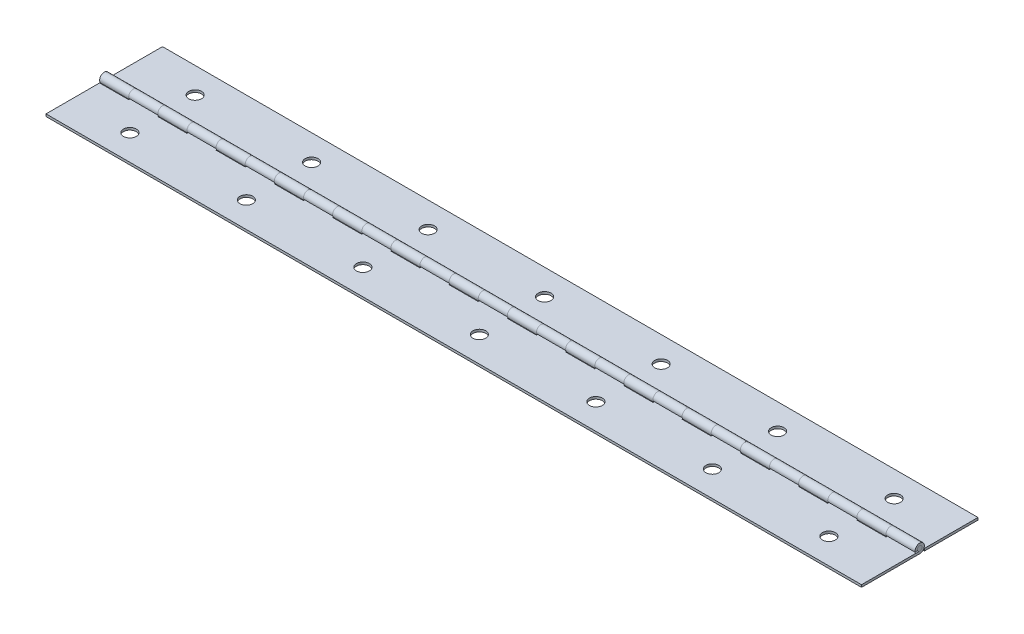
SolidWorks part; units mm, degrees
material "Plain Carbon Steel"
ref_plane "Front Plane" through (0, 0, 0) normal (0, 0, 1) x (1, 0, 0)
ref_plane "Top Plane" through (0, 0, 0) normal (0, 1, 0) x (1, 0, 0)
ref_plane "Right Plane" through (0, 0, 0) normal (1, 0, 0) x (0, 0, -1)
sketch "Sketch1" plane through (0, 0, 0) normal (1, 0, 0) x (0, 0, -1)
  line L0 (25.4, 1.016) -> (0, 1.016)
  line L1 (25.4, 0) -> (0, 0)
  line L2 (1.9675, 1.524) -> (0.9837, 1.778)
  line L3 (25.4, 1.016) -> (25.4, 0)
  circle A0 centre (0, 2.032) radius 1.016 construction
  arc A1 (0, 1.016) -> (0.9837, 1.778) centre (0, 2.032) cw
  arc A2 (0, 0) -> (1.9675, 1.524) centre (0, 2.032) cw
  arc A3 (0, 0) -> (1.9675, 1.524) centre (0, 2.032) cw construction
  dimension "D1" = 2.032
  dimension "D2" = 1.016
  dimension "D3" = 25.4
  dimension "D5" = 0.508
  dimension "D4" = 1.016
extrude "Boss-Extrude1" add sketch "Sketch1" along normal blind 1828.8
sketch "Sketch2" plane through (0, 1.016, 0) normal (0, 1, 0) x (1, 0, 0)
  line L0 (1828.8, 2.032) -> (0, 2.032) construction
  line L1 (12.7, 2.032) -> (25.4, 2.032)
  line L2 (12.7, 2.032) -> (12.7, -2.032)
  line L3 (12.7, -2.032) -> (25.4, -2.032)
  line L4 (25.4, 2.032) -> (25.4, -2.032)
  line L5 (0, -2.032) -> (1828.8, -2.032) construction
  dimension "D1" = 12.7
  dimension "D2" = 12.7
extrude "Cut-Extrude1" cut sketch "Sketch2" against normal through all both and the other way through all
pattern_linear "LPattern1" count 72 spacing 25.4 along (1, 0, 0) of "Cut-Extrude1"
sketch "Sketch3" plane through (0, 0, 0) normal (-1, 0, 0) x (0, 0, 1)
  line L1 (0, 0) -> (-25.4, 0) construction
  line L8 (25.4, 0) -> (0, 0)
  line L9 (25.4, 0) -> (25.4, 1.016)
  line L10 (25.4, 1.016) -> (0, 1.016)
  line L11 (-25.4, 1.016) -> (0, 1.016) construction
  line L12 (0.9837, 1.778) -> (1.9675, 1.524)
  arc A4 (0, 1.016) -> (0.9837, 1.778) centre (0, 2.032) cw
  arc A5 (0, 0) -> (1.9675, 1.524) centre (0, 2.032) cw
extrude "Boss-Extrude2" add sketch "Sketch3" against normal up to surface (1828.8 mm away) separate body up to face at (1828.8, 0.508, -13.716)
sketch "Sketch4" plane through (0, 1.016, 0) normal (0, 1, 0) x (1, 0, 0)
  line L1 (0, -2.032) -> (12.7, -2.032)
  line L2 (0, -2.032) -> (0, 2.032)
  line L3 (0, 2.032) -> (12.7, 2.032)
  line L4 (12.7, -2.032) -> (12.7, 2.032)
extrude "Cut-Extrude2" cut sketch "Sketch4" against normal through all both and the other way through all
pattern_linear "LPattern3" count 72 spacing 25.4 along (1, 0, 0) of "Cut-Extrude2"
sketch "Sketch5" plane through (0, 0, 0) normal (-1, 0, 0) x (0, 0, 1)
  circle A0 centre (0, 2.032) radius 1.016
  arc A1 (0, 1.016) -> (-0.9837, 1.778) centre (0, 2.032) ccw construction
extrude "Boss-Extrude4" add sketch "Sketch5" against normal up to surface (1828.8 mm away) separate body up to face at (1828.8, 1.6081, 8.4015)
hole_wizard "#2 (0.221) Diameter Hole1" positions "Sketch6" profile "Sketch7" hole size "#2" standard "ANSI Inch" end condition through all
sketch "Sketch6" plane through (0, 1.016, 0) normal (0, 1, 0) x (1, 0, 0)
  line L0 (1828.8, -25.4) -> (0, -25.4) construction
  line L1 (0, -25.4) -> (0, -2.032) construction
  point P0 (25.4, -14.224)
  point P12 (76.2, -14.224)
  point P13 (127, -14.224)
  point P14 (177.8, -14.224)
  point P15 (228.6, -14.224)
  point P16 (279.4, -14.224)
  point P17 (330.2, -14.224)
  point P18 (381, -14.224)
  point P19 (431.8, -14.224)
  point P20 (482.6, -14.224)
  point P21 (533.4, -14.224)
  point P22 (584.2, -14.224)
  point P23 (635, -14.224)
  point P24 (685.8, -14.224)
  point P25 (736.6, -14.224)
  point P26 (787.4, -14.224)
  point P27 (838.2, -14.224)
  point P28 (889, -14.224)
  point P29 (939.8, -14.224)
  point P30 (990.6, -14.224)
  point P31 (1041.4, -14.224)
  point P32 (1092.2, -14.224)
  point P33 (1143, -14.224)
  point P34 (1193.8, -14.224)
  point P35 (1244.6, -14.224)
  point P36 (1295.4, -14.224)
  point P37 (1346.2, -14.224)
  point P38 (1397, -14.224)
  point P39 (1447.8, -14.224)
  point P40 (1498.6, -14.224)
  point P41 (1549.4, -14.224)
  point P42 (1600.2, -14.224)
  point P43 (1651, -14.224)
  point P44 (1701.8, -14.224)
  point P45 (1752.6, -14.224)
  point P46 (1803.4, -14.224)
  dimension "D1" = 11.176
  dimension "D2" = 25.4
  dimension "D4" = 50.8
  dimension "D3" = 36
sketch "Sketch7" plane through (25.4, 1.016, 14.224) normal (1, 0, 0) x (0, 0, 1)
  line L0 (0, 0) -> (0, 1.016)
  line L1 (0, 1.016) -> (2.8067, 1.016)
  line L2 (2.8067, 1.016) -> (2.8067, 0)
  line L5 (2.8067, 0) -> (0, 0)
  line L11 (0, -6.35) -> (0, 107.95) construction
  dimension "Thru Hole Dia." = 5.6134
  dimension "Thru Hole Depth" = 1.016
hole_wizard "#2 (0.221) Diameter Hole2" positions "Sketch8" profile "Sketch9" hole size "#2" standard "ANSI Inch" end condition through all
sketch "Sketch8" plane through (0, 1.016, 0) normal (0, 1, 0) x (1, 0, 0)
  line L0 (0, 0) -> (63.5, 0) construction
  line L1 (63.5, 2.032) -> (63.5, -2.032) construction
  line L2 (25.4, 14.224) -> (76.2, 14.224) construction
  point P0 (25.4, 14.224)
  point P18 (76.2, 14.224)
  point P19 (127, 14.224)
  point P20 (177.8, 14.224)
  point P21 (228.6, 14.224)
  point P22 (279.4, 14.224)
  point P23 (330.2, 14.224)
  point P24 (381, 14.224)
  point P25 (431.8, 14.224)
  point P26 (482.6, 14.224)
  point P27 (533.4, 14.224)
  point P28 (584.2, 14.224)
  point P29 (635, 14.224)
  point P30 (685.8, 14.224)
  point P31 (736.6, 14.224)
  point P32 (787.4, 14.224)
  point P33 (838.2, 14.224)
  point P34 (889, 14.224)
  point P35 (939.8, 14.224)
  point P36 (990.6, 14.224)
  point P37 (1041.4, 14.224)
  point P38 (1092.2, 14.224)
  point P39 (1143, 14.224)
  point P40 (1193.8, 14.224)
  point P41 (1244.6, 14.224)
  point P42 (1295.4, 14.224)
  point P43 (1346.2, 14.224)
  point P44 (1397, 14.224)
  point P45 (1447.8, 14.224)
  point P46 (1498.6, 14.224)
  point P47 (1549.4, 14.224)
  point P48 (1600.2, 14.224)
  point P49 (1651, 14.224)
  point P50 (1701.8, 14.224)
  point P51 (1752.6, 14.224)
  point P52 (1803.4, 14.224)
  dimension "D2" = 50.8
  dimension "D1" = 36
sketch "Sketch9" plane through (25.4, 1.016, -14.224) normal (1, 0, 0) x (0, 0, 1)
  line L0 (0, 0) -> (0, 1.016)
  line L1 (0, 1.016) -> (2.8067, 1.016)
  line L2 (2.8067, 1.016) -> (2.8067, 0)
  line L5 (2.8067, 0) -> (0, 0)
  line L11 (0, -6.35) -> (0, 107.95) construction
  dimension "Thru Hole Dia." = 5.6134
  dimension "Thru Hole Depth" = 1.016
sketch "Sketch10" plane through (0, 1.016, 0) normal (0, 1, 0) x (1, 0, 0)
  line L0 (1828.8, 25.4) -> (0, 25.4) construction
  line L1 (355.6, 25.4) -> (1828.8, 25.4)
  line L2 (355.6, 25.4) -> (355.6, -25.4)
  line L3 (355.6, -25.4) -> (1828.8, -25.4)
  line L4 (1828.8, 25.4) -> (1828.8, -25.4)
  line L5 (0, 25.4) -> (0, 0) construction
  dimension "D1" = 355.6
extrude "Cut-Extrude3" cut sketch "Sketch10" against normal through all both and the other way through all
delete or keep bodies "Body-Delete/Keep 1" [suppressed] type delete bodies bodies 112 113
delete or keep bodies "Body-Delete/Keep 2" [suppressed] type delete bodies bodies 112 114
delete or keep bodies "Body-Delete/Keep 3" [suppressed] type delete bodies bodies 113 114
